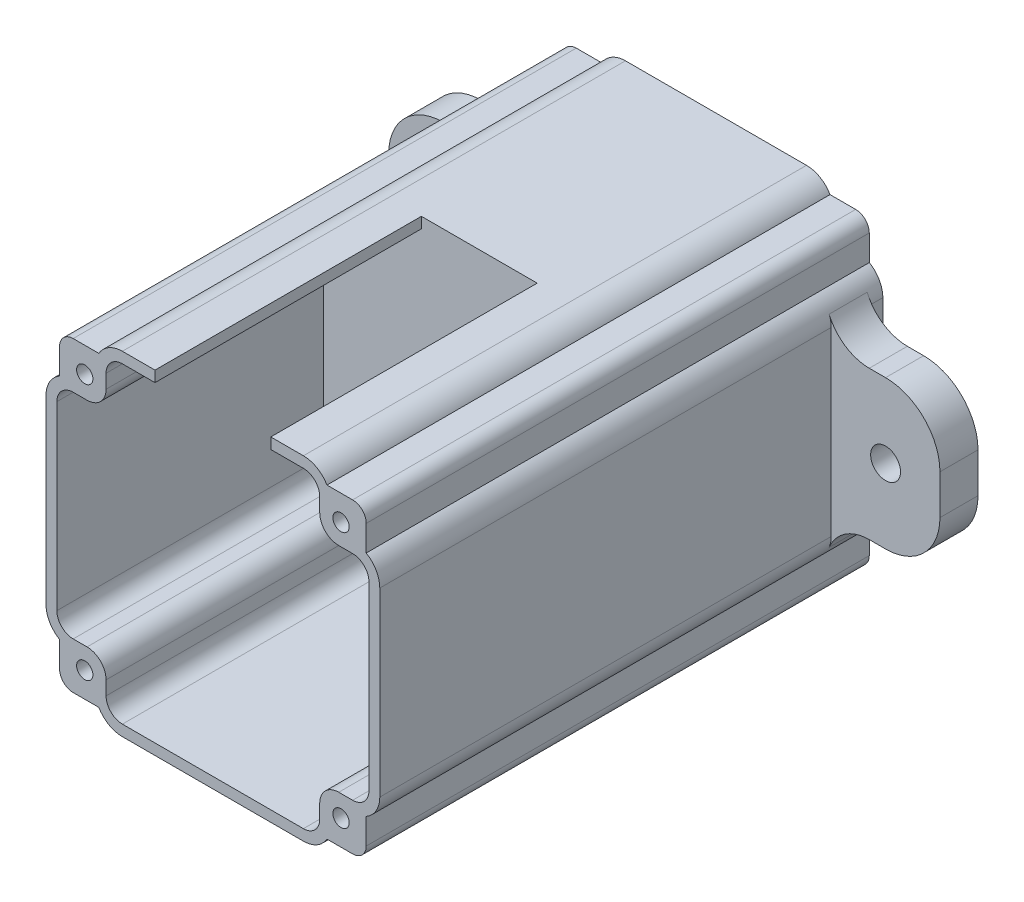
SolidWorks part; units mm, degrees
ref_plane "Front Plane" through (0, 0, 0) normal (0, 0, 1) x (1, 0, 0)
ref_plane "Top Plane" through (0, 0, 0) normal (0, 1, 0) x (1, 0, 0)
ref_plane "Right Plane" through (0, 0, 0) normal (1, 0, 0) x (0, 0, -1)
sketch "Sketch1" plane through (0, 0, -54) normal (0, 0, -1) x (-1, 0, 0)
  line L0 (-25.7, -19.65) -> (-23.15, -19.65)
  line L1 (-19.65, -23.15) -> (-19.65, -25.7)
  line L2 (-16.65, -28.7) -> (16.65, -28.7)
  line L3 (19.65, -25.7) -> (19.65, -23.15)
  line L4 (23.15, -19.65) -> (25.7, -19.65)
  line L5 (28.7, -16.65) -> (28.7, 16.65)
  line L6 (25.7, 19.65) -> (23.15, 19.65)
  line L7 (19.65, 23.15) -> (19.65, 25.7)
  line L8 (16.65, 28.7) -> (10.65, 28.7)
  line L9 (-19.65, 25.7) -> (-19.65, 23.15)
  line L10 (-23.15, 19.65) -> (-25.7, 19.65)
  line L11 (-28.7, 16.65) -> (-28.7, -16.65)
  line L12 (-25.7, -18.65) -> (-23.15, -18.65)
  line L13 (-18.65, -23.15) -> (-18.65, -25.7)
  line L14 (-16.65, -27.7) -> (16.65, -27.7)
  line L15 (18.65, -25.7) -> (18.65, -23.15)
  line L16 (23.15, -18.65) -> (25.7, -18.65)
  line L17 (27.7, -16.65) -> (27.7, 16.65)
  line L18 (25.7, 18.65) -> (23.15, 18.65)
  line L19 (18.65, 23.15) -> (18.65, 25.7)
  line L20 (16.65, 27.7) -> (-16.65, 27.7)
  line L21 (-18.65, 25.7) -> (-18.65, 23.15)
  line L22 (-23.15, 18.65) -> (-25.7, 18.65)
  line L23 (-27.7, 16.65) -> (-27.7, -16.65)
  line L24 (-25.7, -18.65) -> (-23.15, -18.65) construction
  line L25 (-18.65, -23.15) -> (-18.65, -25.7) construction
  line L26 (-16.65, -27.7) -> (16.65, -27.7) construction
  line L27 (18.65, -25.7) -> (18.65, -23.15) construction
  line L28 (23.15, -18.65) -> (25.7, -18.65) construction
  line L29 (27.7, -16.65) -> (27.7, 16.65) construction
  line L30 (25.7, 18.65) -> (23.15, 18.65) construction
  line L31 (18.65, 23.15) -> (18.65, 25.7) construction
  line L32 (16.65, 27.7) -> (-16.65, 27.7) construction
  line L33 (-18.65, 25.7) -> (-18.65, 23.15) construction
  line L34 (-23.15, 18.65) -> (-25.7, 18.65) construction
  line L35 (-27.7, 16.65) -> (-27.7, -16.65) construction
  line L36 (-25.7, -21.65) -> (-23.15, -21.65)
  line L37 (-21.65, -23.15) -> (-21.65, -25.7)
  line L38 (-16.65, -30.7) -> (16.65, -30.7)
  line L39 (21.65, -25.7) -> (21.65, -23.15)
  line L40 (23.15, -21.65) -> (25.7, -21.65)
  line L41 (30.7, -16.65) -> (30.7, 16.65)
  line L42 (25.7, 21.65) -> (23.15, 21.65)
  line L43 (21.65, 23.15) -> (21.65, 25.7)
  line L44 (16.65, 30.7) -> (10.65, 30.7)
  line L45 (-21.65, 25.7) -> (-21.65, 23.15)
  line L46 (-23.15, 21.65) -> (-25.7, 21.65)
  line L47 (-30.7, 16.65) -> (-30.7, -16.65)
  line L48 (-10.65, 30.7) -> (-10.65, 28.7)
  line L49 (10.65, 30.7) -> (10.65, 28.7)
  line L50 (-10.65, 30.7) -> (-16.65, 30.7)
  line L51 (16.65, 30.7) -> (-16.65, 30.7) construction
  line L52 (-10.65, 28.7) -> (-16.65, 28.7)
  line L53 (16.65, 28.7) -> (-16.65, 28.7) construction
  arc A0 (-19.65, -23.15) -> (-23.15, -19.65) centre (-23.15, -23.15) ccw
  arc A1 (-19.65, -25.7) -> (-16.65, -28.7) centre (-16.65, -25.7) ccw
  arc A2 (16.65, -28.7) -> (19.65, -25.7) centre (16.65, -25.7) ccw
  arc A3 (23.15, -19.65) -> (19.65, -23.15) centre (23.15, -23.15) ccw
  arc A4 (25.7, -19.65) -> (28.7, -16.65) centre (25.7, -16.65) ccw
  arc A5 (28.7, 16.65) -> (25.7, 19.65) centre (25.7, 16.65) ccw
  arc A6 (19.65, 23.15) -> (23.15, 19.65) centre (23.15, 23.15) ccw
  arc A7 (19.65, 25.7) -> (16.65, 28.7) centre (16.65, 25.7) ccw
  arc A8 (-16.65, 28.7) -> (-19.65, 25.7) centre (-16.65, 25.7) ccw
  arc A9 (-23.15, 19.65) -> (-19.65, 23.15) centre (-23.15, 23.15) ccw
  arc A10 (-25.7, 19.65) -> (-28.7, 16.65) centre (-25.7, 16.65) ccw
  arc A11 (-28.7, -16.65) -> (-25.7, -19.65) centre (-25.7, -16.65) ccw
  arc A12 (-27.7, -16.65) -> (-25.7, -18.65) centre (-25.7, -16.65) ccw
  arc A13 (-18.65, -23.15) -> (-23.15, -18.65) centre (-23.15, -23.15) ccw
  arc A14 (-18.65, -25.7) -> (-16.65, -27.7) centre (-16.65, -25.7) ccw
  arc A15 (16.65, -27.7) -> (18.65, -25.7) centre (16.65, -25.7) ccw
  arc A16 (23.15, -18.65) -> (18.65, -23.15) centre (23.15, -23.15) ccw
  arc A17 (25.7, -18.65) -> (27.7, -16.65) centre (25.7, -16.65) ccw
  arc A18 (27.7, 16.65) -> (25.7, 18.65) centre (25.7, 16.65) ccw
  arc A19 (18.65, 23.15) -> (23.15, 18.65) centre (23.15, 23.15) ccw
  arc A20 (18.65, 25.7) -> (16.65, 27.7) centre (16.65, 25.7) ccw
  arc A21 (-16.65, 27.7) -> (-18.65, 25.7) centre (-16.65, 25.7) ccw
  arc A22 (-23.15, 18.65) -> (-18.65, 23.15) centre (-23.15, 23.15) ccw
  arc A23 (-25.7, 18.65) -> (-27.7, 16.65) centre (-25.7, 16.65) ccw
  arc A24 (-27.7, -16.65) -> (-25.7, -18.65) centre (-25.7, -16.65) ccw construction
  arc A25 (-18.65, -23.15) -> (-23.15, -18.65) centre (-23.15, -23.15) ccw construction
  arc A26 (-18.65, -25.7) -> (-16.65, -27.7) centre (-16.65, -25.7) ccw construction
  arc A27 (16.65, -27.7) -> (18.65, -25.7) centre (16.65, -25.7) ccw construction
  arc A28 (23.15, -18.65) -> (18.65, -23.15) centre (23.15, -23.15) ccw construction
  arc A29 (25.7, -18.65) -> (27.7, -16.65) centre (25.7, -16.65) ccw construction
  arc A30 (27.7, 16.65) -> (25.7, 18.65) centre (25.7, 16.65) ccw construction
  arc A31 (18.65, 23.15) -> (23.15, 18.65) centre (23.15, 23.15) ccw construction
  arc A32 (18.65, 25.7) -> (16.65, 27.7) centre (16.65, 25.7) ccw construction
  arc A33 (-16.65, 27.7) -> (-18.65, 25.7) centre (-16.65, 25.7) ccw construction
  arc A34 (-23.15, 18.65) -> (-18.65, 23.15) centre (-23.15, 23.15) ccw construction
  arc A35 (-25.7, 18.65) -> (-27.7, 16.65) centre (-25.7, 16.65) ccw construction
  arc A36 (-21.65, -23.15) -> (-23.15, -21.65) centre (-23.15, -23.15) ccw
  arc A37 (-21.65, -25.7) -> (-16.65, -30.7) centre (-16.65, -25.7) ccw
  arc A38 (16.65, -30.7) -> (21.65, -25.7) centre (16.65, -25.7) ccw
  arc A39 (23.15, -21.65) -> (21.65, -23.15) centre (23.15, -23.15) ccw
  arc A40 (25.7, -21.65) -> (30.7, -16.65) centre (25.7, -16.65) ccw
  arc A41 (30.7, 16.65) -> (25.7, 21.65) centre (25.7, 16.65) ccw
  arc A42 (21.65, 23.15) -> (23.15, 21.65) centre (23.15, 23.15) ccw
  arc A43 (21.65, 25.7) -> (16.65, 30.7) centre (16.65, 25.7) ccw
  arc A44 (-16.65, 30.7) -> (-21.65, 25.7) centre (-16.65, 25.7) ccw
  arc A45 (-23.15, 21.65) -> (-21.65, 23.15) centre (-23.15, 23.15) ccw
  arc A46 (-25.7, 21.65) -> (-30.7, 16.65) centre (-25.7, 16.65) ccw
  arc A47 (-30.7, -16.65) -> (-25.7, -21.65) centre (-25.7, -16.65) ccw
  dimension "D4" = 6
  dimension "D5" = 6
  dimension "D1" = 0
  dimension "D2" = 1
  dimension "D3" = 2
extrude "Boss-Extrude1" add sketch "Sketch1" against normal up to surface (49 mm away)
sketch "Sketch2" plane through (0, 0, -54) normal (0, 0, -1) x (-1, 0, 0)
  line L0 (-10.65, 30.7) -> (10.65, 30.7)
  line L12 (-25.7, -21.65) -> (-23.15, -21.65)
  line L13 (-21.65, -23.15) -> (-21.65, -25.7)
  line L14 (-16.65, -30.7) -> (16.65, -30.7)
  line L15 (21.65, -25.7) -> (21.65, -23.15)
  line L16 (23.15, -21.65) -> (25.7, -21.65)
  line L17 (30.7, -16.65) -> (30.7, 16.65)
  line L18 (25.7, 21.65) -> (23.15, 21.65)
  line L19 (21.65, 23.15) -> (21.65, 25.7)
  line L20 (16.65, 30.7) -> (10.65, 30.7)
  line L21 (-21.65, 25.7) -> (-21.65, 23.15)
  line L22 (-23.15, 21.65) -> (-25.7, 21.65)
  line L23 (-30.7, 16.65) -> (-30.7, -16.65)
  line L24 (-25.7, -21.65) -> (-23.15, -21.65)
  line L25 (-21.65, -23.15) -> (-21.65, -25.7)
  line L26 (-16.65, -30.7) -> (16.65, -30.7)
  line L27 (21.65, -25.7) -> (21.65, -23.15)
  line L28 (23.15, -21.65) -> (25.7, -21.65)
  line L29 (30.7, -16.65) -> (30.7, 16.65)
  line L30 (25.7, 21.65) -> (23.15, 21.65)
  line L31 (21.65, 23.15) -> (21.65, 25.7)
  line L32 (16.65, 30.7) -> (10.65, 30.7)
  line L33 (-21.65, 25.7) -> (-21.65, 23.15)
  line L34 (-23.15, 21.65) -> (-25.7, 21.65)
  line L35 (-30.7, 16.65) -> (-30.7, -16.65)
  line L52 (-28.7, -16.65) -> (-28.7, 16.65)
  line L54 (-25.7, 19.65) -> (-23.15, 19.65)
  line L56 (-19.65, 23.15) -> (-19.65, 25.7)
  line L58 (-16.65, 28.7) -> (-10.65, 28.7)
  line L60 (-10.65, 28.7) -> (-10.65, 30.7)
  line L62 (-10.65, 30.7) -> (-16.65, 30.7)
  line L63 (-10.65, 30.7) -> (-16.65, 30.7)
  line L64 (10.65, 30.7) -> (10.65, 28.7)
  line L66 (10.65, 28.7) -> (16.65, 28.7)
  line L68 (19.65, 25.7) -> (19.65, 23.15)
  line L70 (23.15, 19.65) -> (25.7, 19.65)
  line L72 (28.7, 16.65) -> (28.7, -16.65)
  line L74 (25.7, -19.65) -> (23.15, -19.65)
  line L76 (19.65, -23.15) -> (19.65, -25.7)
  line L78 (16.65, -28.7) -> (-16.65, -28.7)
  line L80 (-19.65, -25.7) -> (-19.65, -23.15)
  line L82 (-23.15, -19.65) -> (-25.7, -19.65)
  arc A12 (-30.7, -16.65) -> (-25.7, -21.65) centre (-25.7, -16.65) ccw
  arc A13 (-21.65, -23.15) -> (-23.15, -21.65) centre (-23.15, -23.15) ccw
  arc A14 (-21.65, -25.7) -> (-16.65, -30.7) centre (-16.65, -25.7) ccw
  arc A15 (16.65, -30.7) -> (21.65, -25.7) centre (16.65, -25.7) ccw
  arc A16 (23.15, -21.65) -> (21.65, -23.15) centre (23.15, -23.15) ccw
  arc A17 (25.7, -21.65) -> (30.7, -16.65) centre (25.7, -16.65) ccw
  arc A18 (30.7, 16.65) -> (25.7, 21.65) centre (25.7, 16.65) ccw
  arc A19 (21.65, 23.15) -> (23.15, 21.65) centre (23.15, 23.15) ccw
  arc A20 (21.65, 25.7) -> (16.65, 30.7) centre (16.65, 25.7) ccw
  arc A21 (-16.65, 30.7) -> (-21.65, 25.7) centre (-16.65, 25.7) ccw
  arc A22 (-23.15, 21.65) -> (-21.65, 23.15) centre (-23.15, 23.15) ccw
  arc A23 (-25.7, 21.65) -> (-30.7, 16.65) centre (-25.7, 16.65) ccw
  arc A24 (-30.7, -16.65) -> (-25.7, -21.65) centre (-25.7, -16.65) ccw
  arc A25 (-21.65, -23.15) -> (-23.15, -21.65) centre (-23.15, -23.15) ccw
  arc A26 (-21.65, -25.7) -> (-16.65, -30.7) centre (-16.65, -25.7) ccw
  arc A27 (16.65, -30.7) -> (21.65, -25.7) centre (16.65, -25.7) ccw
  arc A28 (23.15, -21.65) -> (21.65, -23.15) centre (23.15, -23.15) ccw
  arc A29 (25.7, -21.65) -> (30.7, -16.65) centre (25.7, -16.65) ccw
  arc A30 (30.7, 16.65) -> (25.7, 21.65) centre (25.7, 16.65) ccw
  arc A31 (21.65, 23.15) -> (23.15, 21.65) centre (23.15, 23.15) ccw
  arc A32 (21.65, 25.7) -> (16.65, 30.7) centre (16.65, 25.7) ccw
  arc A33 (-16.65, 30.7) -> (-21.65, 25.7) centre (-16.65, 25.7) ccw
  arc A34 (-23.15, 21.65) -> (-21.65, 23.15) centre (-23.15, 23.15) ccw
  arc A35 (-25.7, 21.65) -> (-30.7, 16.65) centre (-25.7, 16.65) ccw
  arc A48 (-28.7, -16.65) -> (-25.7, -19.65) centre (-25.7, -16.65) ccw
  arc A50 (-25.7, 19.65) -> (-28.7, 16.65) centre (-25.7, 16.65) ccw
  arc A52 (-23.15, 19.65) -> (-19.65, 23.15) centre (-23.15, 23.15) ccw
  arc A54 (-16.65, 28.7) -> (-19.65, 25.7) centre (-16.65, 25.7) ccw
  arc A56 (19.65, 25.7) -> (16.65, 28.7) centre (16.65, 25.7) ccw
  arc A58 (19.65, 23.15) -> (23.15, 19.65) centre (23.15, 23.15) ccw
  arc A60 (28.7, 16.65) -> (25.7, 19.65) centre (25.7, 16.65) ccw
  arc A62 (25.7, -19.65) -> (28.7, -16.65) centre (25.7, -16.65) ccw
  arc A64 (23.15, -19.65) -> (19.65, -23.15) centre (23.15, -23.15) ccw
  arc A66 (16.65, -28.7) -> (19.65, -25.7) centre (16.65, -25.7) ccw
  arc A68 (-19.65, -25.7) -> (-16.65, -28.7) centre (-16.65, -25.7) ccw
  arc A70 (-19.65, -23.15) -> (-23.15, -19.65) centre (-23.15, -23.15) ccw
  dimension "D1" = 0
extrude "Boss-Extrude2" add sketch "Sketch2" along normal blind 1.5
sketch "Sketch3" plane through (0, 0, -55.5) normal (0, 0, -1) x (-1, 0, 0)
  line L5 (-21.65, 25.7) -> (-21.65, 23.15) construction
  line L6 (-23.15, 21.65) -> (-25.7, 21.65) construction
  line L7 (-28.2, 16.65) -> (-28.2, 25.7) construction
  line L13 (-25.7, 28.2) -> (-16.65, 28.2) construction
  line L14 (-21.65, 25.7) -> (-21.65, 23.15)
  line L15 (-23.15, 21.65) -> (-25.7, 21.65)
  line L21 (-28.2, 20.9801) -> (-28.2, 25.7)
  line L22 (-25.7, 28.2) -> (-20.9801, 28.2)
  line L23 (21.65, 23.15) -> (21.65, 25.7) construction
  line L92 (25.7, 21.65) -> (23.15, 21.65) construction
  line L93 (28.2, 25.7) -> (28.2, 16.65) construction
  line L94 (16.65, 28.2) -> (25.7, 28.2) construction
  line L95 (21.65, 23.15) -> (21.65, 25.7)
  line L96 (25.7, 21.65) -> (23.15, 21.65)
  line L97 (28.2, 25.7) -> (28.2, 20.9801)
  line L98 (20.9801, 28.2) -> (25.7, 28.2)
  line L99 (-25.7, -21.65) -> (-23.15, -21.65) construction
  line L100 (-21.65, -23.15) -> (-21.65, -25.7) construction
  line L101 (-16.65, -28.2) -> (-25.7, -28.2) construction
  line L102 (-28.2, -25.7) -> (-28.2, -16.65) construction
  line L103 (-25.7, -21.65) -> (-23.15, -21.65)
  line L104 (-21.65, -23.15) -> (-21.65, -25.7)
  line L105 (-20.9801, -28.2) -> (-25.7, -28.2)
  line L106 (-28.2, -25.7) -> (-28.2, -20.9801)
  line L107 (25.7, -28.2) -> (16.65, -28.2) construction
  line L108 (21.65, -25.7) -> (21.65, -23.15) construction
  line L109 (23.15, -21.65) -> (25.7, -21.65) construction
  line L110 (25.7, -28.2) -> (20.9801, -28.2)
  line L111 (21.65, -25.7) -> (21.65, -23.15)
  line L112 (23.15, -21.65) -> (25.7, -21.65)
  line L113 (28.2, -16.65) -> (28.2, -25.7) construction
  line L114 (28.2, -20.9801) -> (28.2, -25.7)
  arc A92 (-16.65, 30.7) -> (-21.65, 25.7) centre (-16.65, 25.7) ccw construction
  arc A93 (-23.15, 21.65) -> (-21.65, 23.15) centre (-23.15, 23.15) ccw construction
  arc A94 (-25.7, 21.65) -> (-30.7, 16.65) centre (-25.7, 16.65) ccw construction
  arc A95 (-25.7, 28.2) -> (-28.2, 25.7) centre (-25.7, 25.7) ccw construction
  arc A96 (-20.9801, 28.2) -> (-21.65, 25.7) centre (-16.65, 25.7) ccw
  arc A97 (-23.15, 21.65) -> (-21.65, 23.15) centre (-23.15, 23.15) ccw
  arc A98 (-25.7, 21.65) -> (-28.2, 20.9801) centre (-25.7, 16.65) ccw
  arc A99 (-25.7, 28.2) -> (-28.2, 25.7) centre (-25.7, 25.7) ccw
  arc A100 (21.65, 25.7) -> (16.65, 30.7) centre (16.65, 25.7) ccw construction
  arc A101 (21.65, 23.15) -> (23.15, 21.65) centre (23.15, 23.15) ccw construction
  arc A102 (30.7, 16.65) -> (25.7, 21.65) centre (25.7, 16.65) ccw construction
  arc A103 (28.2, 25.7) -> (25.7, 28.2) centre (25.7, 25.7) ccw construction
  arc A104 (21.65, 25.7) -> (20.9801, 28.2) centre (16.65, 25.7) ccw
  arc A105 (21.65, 23.15) -> (23.15, 21.65) centre (23.15, 23.15) ccw
  arc A106 (28.2, 20.9801) -> (25.7, 21.65) centre (25.7, 16.65) ccw
  arc A107 (28.2, 25.7) -> (25.7, 28.2) centre (25.7, 25.7) ccw
  arc A108 (-30.7, -16.65) -> (-25.7, -21.65) centre (-25.7, -16.65) ccw construction
  arc A109 (-21.65, -23.15) -> (-23.15, -21.65) centre (-23.15, -23.15) ccw construction
  arc A110 (-21.65, -25.7) -> (-16.65, -30.7) centre (-16.65, -25.7) ccw construction
  arc A111 (-28.2, -25.7) -> (-25.7, -28.2) centre (-25.7, -25.7) ccw construction
  arc A112 (-28.2, -20.9801) -> (-25.7, -21.65) centre (-25.7, -16.65) ccw
  arc A113 (-21.65, -23.15) -> (-23.15, -21.65) centre (-23.15, -23.15) ccw
  arc A114 (-21.65, -25.7) -> (-20.9801, -28.2) centre (-16.65, -25.7) ccw
  arc A115 (-28.2, -25.7) -> (-25.7, -28.2) centre (-25.7, -25.7) ccw
  arc A116 (25.7, -28.2) -> (28.2, -25.7) centre (25.7, -25.7) ccw construction
  arc A117 (16.65, -30.7) -> (21.65, -25.7) centre (16.65, -25.7) ccw construction
  arc A118 (23.15, -21.65) -> (21.65, -23.15) centre (23.15, -23.15) ccw construction
  arc A119 (25.7, -21.65) -> (30.7, -16.65) centre (25.7, -16.65) ccw construction
  arc A120 (25.7, -28.2) -> (28.2, -25.7) centre (25.7, -25.7) ccw
  arc A121 (20.9801, -28.2) -> (21.65, -25.7) centre (16.65, -25.7) ccw
  arc A122 (23.15, -21.65) -> (21.65, -23.15) centre (23.15, -23.15) ccw
  arc A123 (25.7, -21.65) -> (28.2, -20.9801) centre (25.7, -16.65) ccw
extrude "Boss-Extrude3" add sketch "Sketch3" against normal up to surface (50.5 mm away) region at (24.8618, 24.8618, -55.5) region at (-24.8618, 24.8618, -55.5) region at (24.8618, -24.8618, -55.5) region at (-24.8618, -24.8618, -55.5)
sketch "Sketch4" plane through (0, 0, -5) normal (0, 0, 1) x (1, 0, 0)
  circle A0 centre (-23.57, 23.57) radius 1.5
  circle A1 centre (23.57, 23.57) radius 1.5
  circle A2 centre (-23.57, -23.57) radius 1.5
  circle A3 centre (23.57, -23.57) radius 1.5
  dimension "D1" = 3
extrude "Cut-Extrude1" cut sketch "Sketch4" against normal blind 10
sketch "Sketch5" plane through (0, 0, -55.5) normal (0, 0, -1) x (-1, 0, 0)
  line L12 (28.2, -25.7) -> (28.2, -20.9801)
  line L13 (30.7, -16.65) -> (30.7, 16.65)
  line L14 (28.2, 20.9801) -> (28.2, 25.7)
  line L15 (25.7, 28.2) -> (20.9801, 28.2)
  line L16 (16.65, 30.7) -> (-16.65, 30.7)
  line L17 (-20.9801, 28.2) -> (-25.7, 28.2)
  line L18 (-28.2, 25.7) -> (-28.2, 20.9801)
  line L19 (-30.7, 16.65) -> (-30.7, -16.65)
  line L20 (-28.2, -20.9801) -> (-28.2, -25.7)
  line L21 (-25.7, -28.2) -> (-20.9801, -28.2)
  line L22 (-16.65, -30.7) -> (16.65, -30.7)
  line L23 (20.9801, -28.2) -> (25.7, -28.2)
  line L24 (28.2, -25.7) -> (28.2, -20.9801)
  line L25 (30.7, -16.65) -> (30.7, 16.65)
  line L26 (28.2, 20.9801) -> (28.2, 25.7)
  line L27 (25.7, 28.2) -> (20.9801, 28.2)
  line L28 (16.65, 30.7) -> (-16.65, 30.7)
  line L29 (-20.9801, 28.2) -> (-25.7, 28.2)
  line L30 (-28.2, 25.7) -> (-28.2, 20.9801)
  line L31 (-30.7, 16.65) -> (-30.7, -16.65)
  line L32 (-28.2, -20.9801) -> (-28.2, -25.7)
  line L33 (-25.7, -28.2) -> (-20.9801, -28.2)
  line L34 (-16.65, -30.7) -> (16.65, -30.7)
  line L35 (20.9801, -28.2) -> (25.7, -28.2)
  arc A12 (28.2, -20.9801) -> (30.7, -16.65) centre (25.7, -16.65) ccw
  arc A13 (30.7, 16.65) -> (28.2, 20.9801) centre (25.7, 16.65) ccw
  arc A14 (28.2, 25.7) -> (25.7, 28.2) centre (25.7, 25.7) ccw
  arc A15 (20.9801, 28.2) -> (16.65, 30.7) centre (16.65, 25.7) ccw
  arc A16 (-16.65, 30.7) -> (-20.9801, 28.2) centre (-16.65, 25.7) ccw
  arc A17 (-25.7, 28.2) -> (-28.2, 25.7) centre (-25.7, 25.7) ccw
  arc A18 (-28.2, 20.9801) -> (-30.7, 16.65) centre (-25.7, 16.65) ccw
  arc A19 (-30.7, -16.65) -> (-28.2, -20.9801) centre (-25.7, -16.65) ccw
  arc A20 (-28.2, -25.7) -> (-25.7, -28.2) centre (-25.7, -25.7) ccw
  arc A21 (-20.9801, -28.2) -> (-16.65, -30.7) centre (-16.65, -25.7) ccw
  arc A22 (16.65, -30.7) -> (20.9801, -28.2) centre (16.65, -25.7) ccw
  arc A23 (25.7, -28.2) -> (28.2, -25.7) centre (25.7, -25.7) ccw
  arc A24 (28.2, -20.9801) -> (30.7, -16.65) centre (25.7, -16.65) ccw
  arc A25 (30.7, 16.65) -> (28.2, 20.9801) centre (25.7, 16.65) ccw
  arc A26 (28.2, 25.7) -> (25.7, 28.2) centre (25.7, 25.7) ccw
  arc A27 (20.9801, 28.2) -> (16.65, 30.7) centre (16.65, 25.7) ccw
  arc A28 (-16.65, 30.7) -> (-20.9801, 28.2) centre (-16.65, 25.7) ccw
  arc A29 (-25.7, 28.2) -> (-28.2, 25.7) centre (-25.7, 25.7) ccw
  arc A30 (-28.2, 20.9801) -> (-30.7, 16.65) centre (-25.7, 16.65) ccw
  arc A31 (-30.7, -16.65) -> (-28.2, -20.9801) centre (-25.7, -16.65) ccw
  arc A32 (-28.2, -25.7) -> (-25.7, -28.2) centre (-25.7, -25.7) ccw
  arc A33 (-20.9801, -28.2) -> (-16.65, -30.7) centre (-16.65, -25.7) ccw
  arc A34 (16.65, -30.7) -> (20.9801, -28.2) centre (16.65, -25.7) ccw
  arc A35 (25.7, -28.2) -> (28.2, -25.7) centre (25.7, -25.7) ccw
  dimension "D1" = 0
extrude "Boss-Extrude4" add sketch "Sketch5" along normal up to surface (42.04 mm away)
sketch "Sketch7" plane through (30.7, 0, 0) normal (1, 0, 0) x (0, 0, -1)
  line L1 (95.04, 13.65) -> (88.04, 13.65)
  line L2 (95.04, 13.65) -> (95.04, -13.65)
  line L3 (95.04, -13.65) -> (88.04, -13.65)
  line L4 (88.04, 13.65) -> (88.04, -13.65)
  line L5 (5, 16.65) -> (97.54, 16.65) construction
  line L6 (5, -16.65) -> (97.54, -16.65) construction
  line L8 (97.54, -16.65) -> (97.54, 16.65) construction
  dimension "D1" = 7
  dimension "D2" = 3
  dimension "D3" = 3
  dimension "D4" = 2.5
extrude "Boss-Extrude5" add sketch "Sketch7" along normal blind 20
fillet "Fillet1" radius 10 2 edges at (50.7, -13.65, -91.54) (50.7, 13.65, -91.54)
fillet "Fillet2" radius 8 2 edges at (30.7, -13.65, -91.54) (30.7, 13.65, -91.54)
mirror "Mirror1" about plane through (0, 0, 0) normal (1, 0, 0) of "Boss-Extrude5"
fillet "Fillet3" radius 10 2 edges at (-50.7, 13.65, -91.54) (-50.7, -13.65, -91.54)
fillet "Fillet4" radius 8 2 edges at (-30.7, -13.65, -91.54) (-30.7, 13.65, -91.54)
sketch "Sketch8" plane through (0, 0, -88.04) normal (0, 0, 1) x (1, 0, 0)
  line L0 (-40.7, 0) -> (40.7, 0) construction
  line L1 (50.7, 3.65) -> (50.7, -3.65) construction
  circle A0 centre (40.7, 0) radius 2.75
  circle A1 centre (-40.7, 0) radius 2.75
  point P4 (0, 0)
  dimension "D1" = 5.5
  dimension "D2" = 10
extrude "Cut-Extrude2" cut sketch "Sketch8" against normal up to surface (9.5 mm away) up to face at (0, 0, -97.54)
